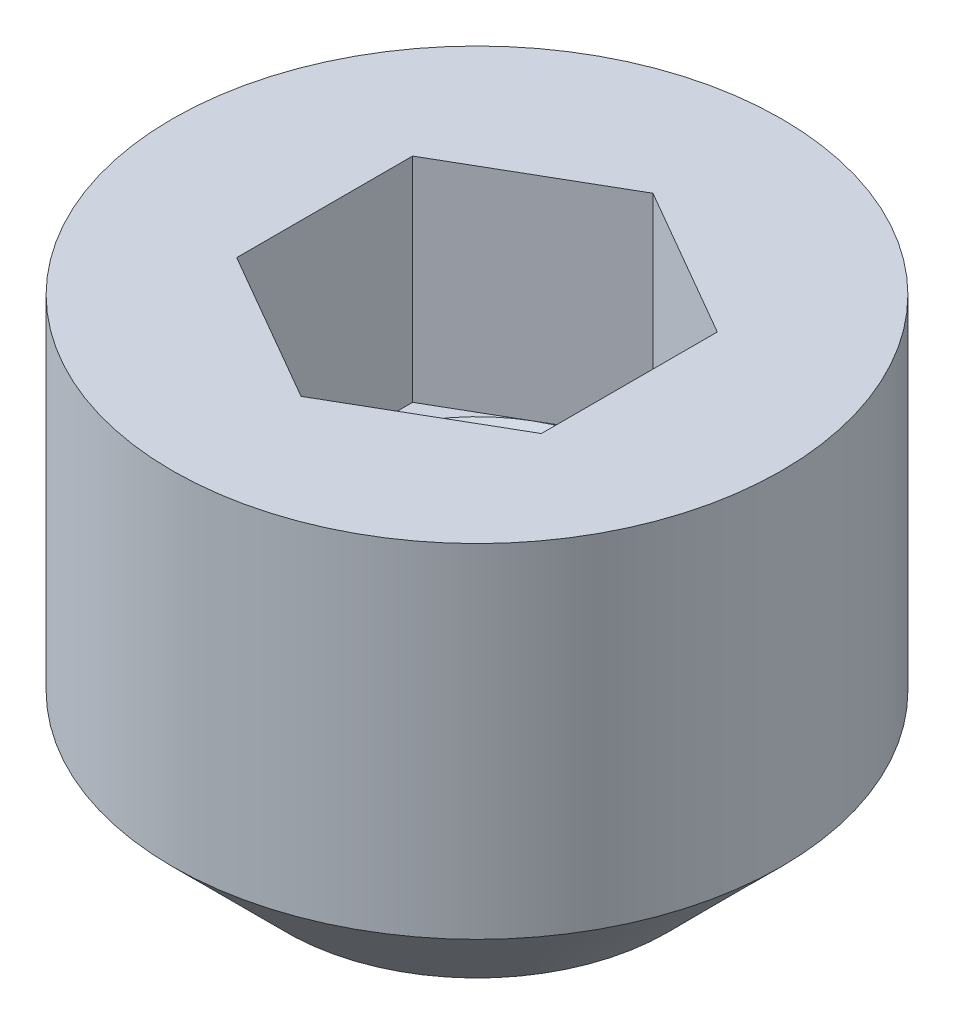
SolidWorks part; units mm, degrees
ref_plane "Front Plane" through (0, 0, 0) normal (0, 0, 1) x (1, 0, 0)
ref_plane "Top Plane" through (0, 0, 0) normal (0, 1, 0) x (1, 0, 0)
ref_plane "Right Plane" through (0, 0, 0) normal (1, 0, 0) x (0, 0, -1)
ref_axis "Axis_X" through (-88.99, 0, 0) along (1, 0, 0)
ref_axis "Axis_Y" through (0, 56.5, 0) along (0, -1, 0)
ref_axis "Axis_Z" through (0, 0, -88.99) along (0, 0, 1)
sketch "Sketch1" plane through (0, 0, 0) normal (0, 0, 1) x (1, 0, 0)
  line L0 (0, 3) -> (0, 0) construction
  line L2 (0, 3) -> (2, 3)
  line L3 (0, 3) -> (0, 0)
  line L4 (0, 0) -> (2, 0)
  line L5 (2, 3) -> (2, 0)
  dimension "SS_M" = 4
  dimension "SS_L" = 3
revolve "Revolve1" add sketch "Sketch1" angle 360 about L0
cosmetic thread "Cosmetic Thread1" parameters "SS_D1_s"=3.242
sketch "Sketch2" plane through (0, 0, 0) normal (0, 0, 1) x (1, 0, 0)
  line L0 (0, 3) -> (0, 1.0226) construction
  line L1 (0, 3) -> (1, 3)
  line L3 (1, 3) -> (1, 1.6)
  line L4 (1, 1.6) -> (0, 1.0226)
  line L5 (0, 1.0226) -> (0, 3)
  line L6 (2, 3) -> (-2, 3) construction
  dimension "D1" = 60
  dimension "SS_B" = 2
  dimension "SS_C" = 1.4
revolve "Cut-Revolve1" cut sketch "Sketch2" angle 360 about L0
sketch "Sketch3" plane through (0, 3, 0) normal (0, 1, 0) x (1, 0, 0)
  line L1 (0, 1.1547) -> (-1, 0.5774)
  line L2 (-1, 0.5774) -> (-1, -0.5774)
  line L3 (-1, -0.5774) -> (0, -1.1547)
  line L4 (0, -1.1547) -> (1, -0.5774)
  line L5 (1, -0.5774) -> (1, 0.5774)
  line L6 (1, 0.5774) -> (0, 1.1547)
  circle A0 centre (0, 0) radius 1 construction
  circle A1 centre (0, 0) radius 1 construction
extrude "Cut-Extrude1" cut sketch "Sketch3" against normal blind 1.4
sketch "Sketch4" plane through (0, 0, 0) normal (0, 0, 1) x (1, 0, 0)
  line L0 (0, 3) -> (0, 0) construction
  line L1 (2, 3) -> (2, 0) construction
  line L2 (-2, 0) -> (2, 0) construction
  line L3 (2, 0.75) -> (2, 0)
  line L4 (2, 0) -> (1.25, 0)
  line L5 (1.25, 0) -> (2, 0.75)
  dimension "D1" = 45
  dimension "SS_D_s" = 2.5
revolve "Cut-Revolve2" cut sketch "Sketch4" angle 360 about L0
